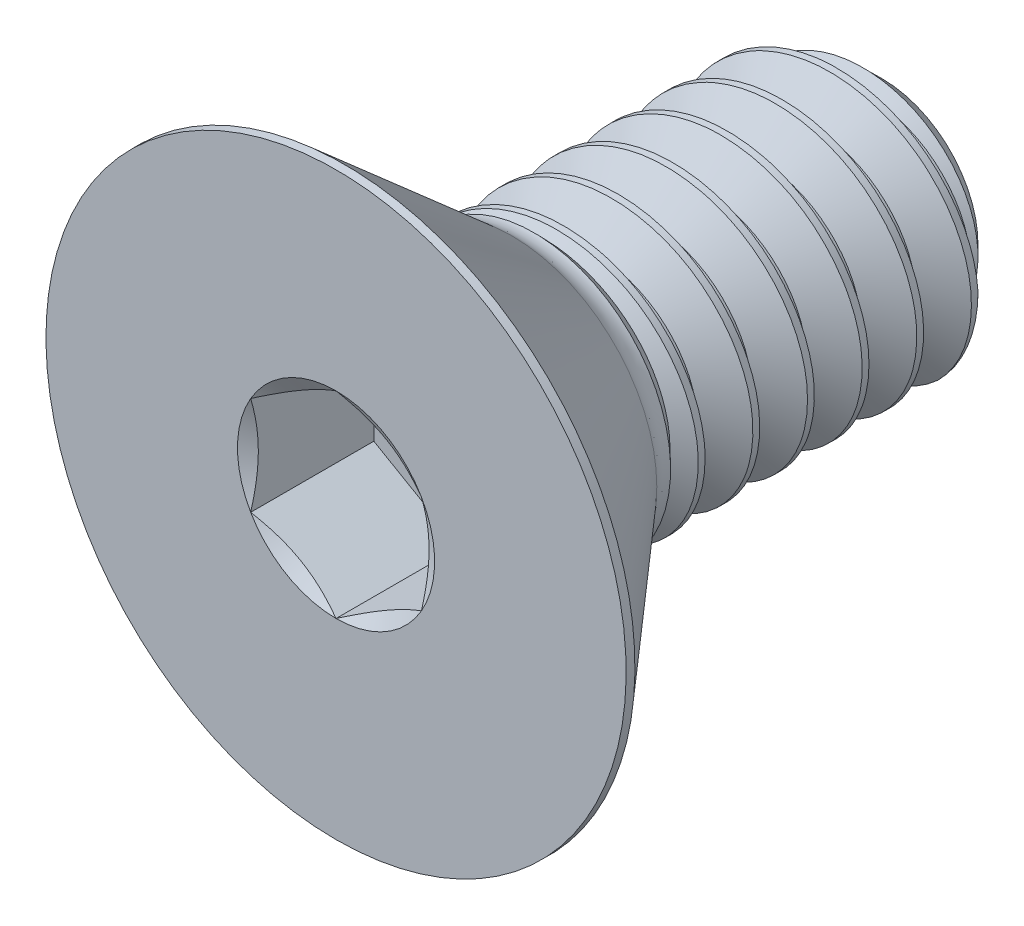
SolidWorks part; units mm, degrees
material "Plain Carbon Steel"
ref_plane "Front" through (0, 0, 0) normal (0, 0, 1) x (1, 0, 0)
ref_plane "Top" through (0, 0, 0) normal (0, 1, 0) x (1, 0, 0)
ref_plane "Right" through (0, 0, 0) normal (1, 0, 0) x (0, 0, -1)
sketch "Sketch1" plane through (0, 0, 0) normal (1, 0, 0) x (0, 0, -1)
  line L0 (0, 6.7437) -> (0.2045, 6.7437) construction
  line L1 (0.2045, 6.7437) -> (4.0894, 3.3666) construction
  line L2 (0, 3.175) -> (12.7, 3.175)
  line L3 (12.7, 3.175) -> (12.7, 0)
  line L4 (12.7, 0) -> (0, 0)
  line L5 (0, 0) -> (0, 6.7437) construction
  line L6 (0, 6.7437) -> (0, -6.7437) construction
  line L7 (12.7, 3.175) -> (12.7, -3.175) construction
  line L8 (0, -6.7437) -> (0.2045, -6.7437) construction
  line L9 (0.2045, -6.7437) -> (4.0894, -3.3666) construction
  line L11 (0, 3.175) -> (0, 0)
  line L12 (4.6018, 3.175) -> (4.6018, 0) construction
  line L13 (-12.7, 0) -> (-12.7, 3.175) construction
  arc A1 (4.0894, 3.3666) -> (4.6018, 3.175) centre (4.6018, 3.956) ccw construction
  dimension "D1" = 0.2045
  dimension "Head Ht" = 4.0894
  dimension "Head Dia" = 13.4874
  dimension "Dia" = 6.35
  dimension "Lg" = 12.7
  dimension "Head Angle" = 82
  dimension "Min Thread" = 25.4
revolve "Revolve1" add sketch "Sketch1" angle 360 mid plane about L4
sketch "Sketch3" plane through (0, 0, -12.7) normal (0, 0, -1) x (-1, 0, 0)
  circle A0 centre (0, 0) radius 3.175
curve "Helix/Spiral1" pitch 1.27 height 12.7 radius 3.175 centre (0, 0, -12.7) axis (0, 0, 1) start towards (0, 1, 0)
sketch "Sketch2" plane through (0, 0, 0) normal (1, 0, 0) x (0, 0, -1)
  line L0 (12.7, 3.175) -> (13.8112, 3.175)
  line L1 (13.8112, 3.175) -> (13.335, 2.3501)
  line L2 (13.335, 2.3501) -> (13.1762, 2.3501)
  line L3 (13.1762, 2.3501) -> (12.7, 3.175)
  line L4 (12.9381, 2.7626) -> (13.5731, 2.7626) construction
  dimension "D1" = 60
  dimension "D2" = 0.1588
  dimension "D3" = 0.635
ref_plane "Plane2" through (0, 0, 12.7) normal (0, 0, 1) x (1, 0, 0)
chamfer "Chamfer1" distance 0.9525 angle 45 1 edges at (0, 3.175, -12.7)
sweep "Cut-Sweep1" cut profiles "Sketch2" path "Helix/Spiral1"
sketch "Sketch7" plane through (0, 0, 0) normal (1, 0, 0) x (0, 0, -1)
  line L0 (0, 6.7437) -> (0.2045, 6.7437) construction
  line L1 (0.2045, 6.7437) -> (4.0894, 3.3666) construction
  line L2 (0, 6.7437) -> (0.2045, 6.7437)
  line L3 (0.2045, 6.7437) -> (4.0894, 3.3666)
  line L4 (4.6018, 3.175) -> (4.6018, 0) construction
  line L5 (4.6018, 3.175) -> (4.6018, 0)
  line L7 (0, 0) -> (0, 6.7437) construction
  line L8 (0, 0) -> (0, 6.7437)
  line L9 (0, 0) -> (4.6018, 0)
  line L10 (5.7417, 0) -> (-5.7417, 0) construction
  arc A0 (4.0894, 3.3666) -> (4.6018, 3.175) centre (4.6018, 3.956) ccw construction
  arc A1 (4.0894, 3.3666) -> (4.6018, 3.175) centre (4.6018, 3.956) ccw
revolve "Revolve2" add sketch "Sketch7" angle 360 mid plane about L9
ref_plane "Plane1" through (0, 0, -4.6018) normal (0, 0, 1) x (1, 0, 0)
sketch "Sketch8" plane through (0, 0, -4.6018) normal (0, 0, 1) x (1, 0, 0)
  circle A0 centre (0, 0) radius 3.175
extrude "Boss-Extrude1" add sketch "Sketch8" against normal through all draft 46
sketch "Sketch5" plane through (0, 0, 0) normal (0, 0, 1) x (1, 0, 0)
  line L0 (0, 0) -> (-2.2914, 0) construction
  line L1 (0, 0) -> (-2.7496, 1.5875) construction
  line L2 (0, 0) -> (-2.7496, -1.5875) construction
  line L6 (0, 2.2914) -> (0, 1.8898) construction
  line L7 (0, 1.8898) -> (0, 1.4883) construction
  line L9 (0, 2.2914) -> (-1.9844, 1.1457)
  line L10 (-1.9844, 1.1457) -> (-1.9844, -1.1457)
  line L11 (-1.9844, -1.1457) -> (0, -2.2914)
  line L12 (0, -2.2914) -> (1.9844, -1.1457)
  line L13 (1.9844, -1.1457) -> (1.9844, 1.1457)
  line L14 (1.9844, 1.1457) -> (0, 2.2914)
  circle A0 centre (0, 0) radius 2.2914 construction
  circle A1 centre (0, 0) radius 1.8898 construction
  circle A2 centre (0, 0) radius 1.4883 construction
  circle A3 centre (0, 0) radius 1.9844 construction
  dimension "D3" = 2.9766
  dimension "Hex" = 3.9688
  dimension "D4" = 30
  dimension "D5" = 30
extrude "Cut-Extrude2" cut sketch "Sketch5" against normal blind 2.8626
sketch "Sketch6" plane through (0, 0, 0) normal (0, 0, 1) x (1, 0, 0)
  circle A0 centre (0, 0) radius 2.2914
extrude "Cut-Extrude3" cut sketch "Sketch6" against normal blind 2.8626 draft 60
sketch "Sketch9" [suppressed] plane through (0, 0, -3.6076) normal (0, 0, 1) x (1, 0, 0)
  circle A1 centre (0, 0) radius 2.413
  circle A2 centre (0, 0) radius 2.413
  point P0 (0, 2.413)
  dimension "D1" = 0
extrude "Boss-Extrude2" [suppressed] add sketch "Sketch9" against normal up to surface (15.4424 mm away) up to plane "Plane2"
sketch "Sketch10" plane through (0, 0, 0) normal (1, 0, 0) x (0, 0, -1)
  line L0 (12.7, 3.175) -> (12.7, -3.175) construction
  point P0 (10.795, -3.175)
  dimension "D1" = 1.905
equation "\"D3@Helix/Spiral1\" = \"Lg@Sketch1\""
equation "\"D2@Sketch2\" = \"D4@Helix/Spiral1\" * .125"
equation "\"D3@Sketch2\" = \"D4@Helix/Spiral1\" * .5"
equation "\"D1@Chamfer1\" = \"D4@Helix/Spiral1\" * .75"
equation "\"D1@Cut-Extrude2\" = \"Head Ht@Sketch1\" * .7"
equation "\"D1@Sketch1\" = \"Head Ht@Sketch1\" * .05"
equation "\"D1@Sketch10\" = \"D4@Helix/Spiral1\" * 1.5"
equation "\"D1@Cut-Extrude3\" = \"D1@Cut-Extrude2\""
equation "\"D3@Sketch5\" = \"Hex@Sketch5\" * .75"
